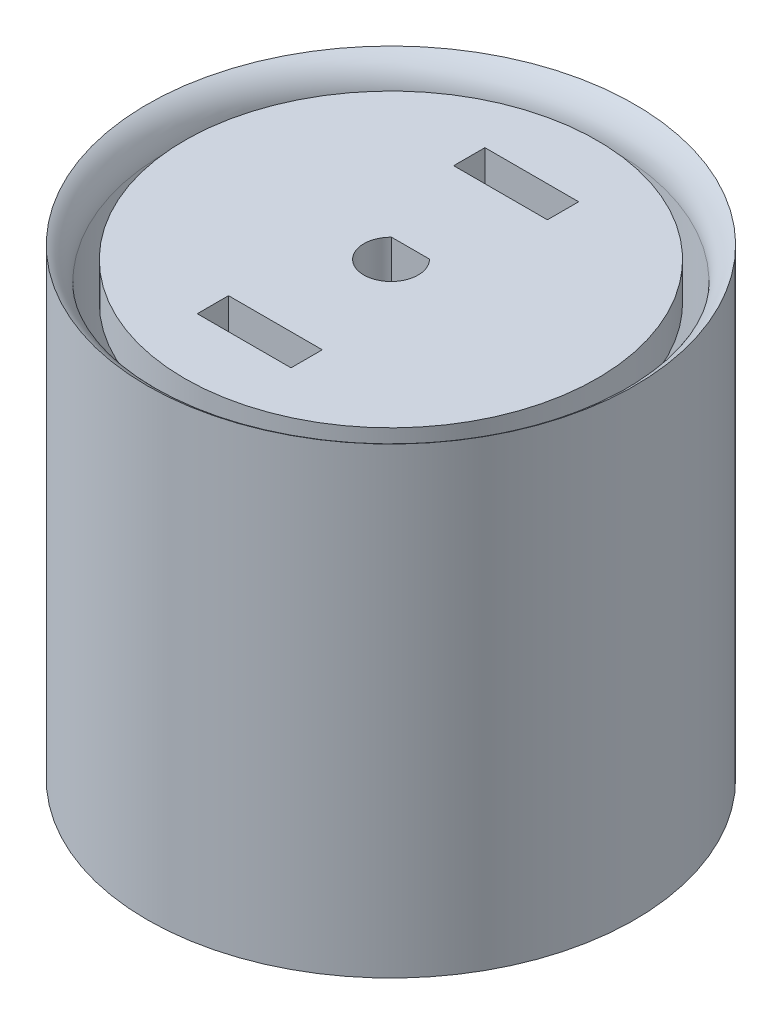
SolidWorks part; units mm, degrees
ref_plane "Front Plane" through (0, 0, 0) normal (0, 0, 1) x (1, 0, 0)
ref_plane "Top Plane" through (0, 0, 0) normal (0, 1, 0) x (1, 0, 0)
ref_plane "Right Plane" through (0, 0, 0) normal (1, 0, 0) x (0, 0, -1)
ref_plane "Plane1" through (0, -15, 0) normal (0, 1, 0) x (1, 0, 0)
ref_plane "Plane2" through (0, 21, 0) normal (0, 1, 0) x (1, 0, 0)
sketch "Sketch1" plane through (0, -15, 0) normal (0, 1, 0) x (1, 0, 0)
  circle A0 centre (0, 0) radius 17
  dimension "D1" = 34
extrude "Boss-Extrude1" add sketch "Sketch1" along normal blind 3
sketch "Sketch3" plane through (0, 21, 0) normal (0, 1, 0) x (1, 0, 0)
  circle A0 centre (0, 0) radius 17
  dimension "D1" = 34
extrude "Boss-Extrude2" add sketch "Sketch3" against normal blind 3 separate body
ref_plane "Plane3" through (0, -12, 0) normal (0, 1, 0) x (1, 0, 0)
sketch "Sketch6" plane through (0, -12, 0) normal (0, 1, 0) x (1, 0, 0)
  line L0 (-10.3961, -6.8606) -> (-11.6878, -8.1522)
  line L1 (-11.6878, -8.1522) -> (-12.2448, -7.2889)
  line L2 (-12.2448, -7.2889) -> (-12.7381, -6.3877)
  line L3 (-12.7381, -6.3877) -> (-13.1653, -5.4532)
  line L4 (-13.1653, -5.4532) -> (-13.524, -4.4905)
  line L5 (-13.524, -4.4905) -> (-13.8124, -3.5043)
  line L6 (-13.8124, -3.5043) -> (-14.029, -2.5)
  line L7 (-14.029, -2.5) -> (-12.2023, -2.5)
  line L8 (-12.2023, -2.5) -> (-12.2023, 2.5)
  line L9 (-12.2023, 2.5) -> (-14.029, 2.5)
  line L10 (-14.029, 2.5) -> (-13.8124, 3.5043)
  line L11 (-13.8124, 3.5043) -> (-13.524, 4.4905)
  line L12 (-13.524, 4.4905) -> (-13.1653, 5.4532)
  line L13 (-13.1653, 5.4532) -> (-12.7381, 6.3877)
  line L14 (-12.7381, 6.3877) -> (-12.2448, 7.2889)
  line L15 (-12.2448, 7.2889) -> (-11.6878, 8.1522)
  line L16 (-11.6878, 8.1522) -> (-10.3961, 6.8606)
  line L17 (-10.3961, 6.8606) -> (-6.8606, 10.3961)
  line L18 (-6.8606, 10.3961) -> (-8.1522, 11.6878)
  line L19 (-8.1522, 11.6878) -> (-7.2889, 12.2448)
  line L20 (-7.2889, 12.2448) -> (-6.3877, 12.7381)
  line L21 (-6.3877, 12.7381) -> (-5.4532, 13.1653)
  line L22 (-5.4532, 13.1653) -> (-4.4905, 13.524)
  line L23 (-4.4905, 13.524) -> (-3.5043, 13.8124)
  line L24 (-3.5043, 13.8124) -> (-2.5, 14.029)
  line L25 (-2.5, 14.029) -> (-2.5, 12.1742)
  line L26 (-2.5, 12.1742) -> (2.5, 12.2023)
  line L27 (2.5, 12.2023) -> (2.5, 14.029)
  line L28 (2.5, 14.029) -> (3.5043, 13.8124)
  line L29 (3.5043, 13.8124) -> (4.4905, 13.524)
  line L30 (4.4905, 13.524) -> (5.4532, 13.1653)
  line L31 (5.4532, 13.1653) -> (6.3877, 12.7381)
  line L32 (6.3877, 12.7381) -> (7.2889, 12.2448)
  line L33 (7.2889, 12.2448) -> (8.1522, 11.6878)
  line L34 (8.1522, 11.6878) -> (6.8606, 10.3961)
  line L35 (6.8606, 10.3961) -> (10.3961, 6.8606)
  line L36 (10.3961, 6.8606) -> (11.6878, 8.1522)
  line L37 (11.6878, 8.1522) -> (12.2448, 7.2889)
  line L38 (12.2448, 7.2889) -> (12.7381, 6.3877)
  line L39 (12.7381, 6.3877) -> (13.1653, 5.4532)
  line L40 (13.1653, 5.4532) -> (13.524, 4.4905)
  line L41 (13.524, 4.4905) -> (13.8124, 3.5043)
  line L42 (13.8124, 3.5043) -> (14.029, 2.5)
  line L43 (14.029, 2.5) -> (12.2023, 2.5)
  line L44 (12.2023, 2.5) -> (12.2023, -2.5)
  line L45 (12.2023, -2.5) -> (14.029, -2.5)
  line L46 (14.029, -2.5) -> (13.8124, -3.5043)
  line L47 (13.8124, -3.5043) -> (13.524, -4.4905)
  line L48 (13.524, -4.4905) -> (13.1653, -5.4532)
  line L49 (13.1653, -5.4532) -> (12.7381, -6.3877)
  line L50 (12.7381, -6.3877) -> (12.2448, -7.2889)
  line L51 (12.2448, -7.2889) -> (11.6878, -8.1522)
  line L52 (11.6878, -8.1522) -> (10.3961, -6.8606)
  line L53 (10.3961, -6.8606) -> (6.8606, -10.3961)
  line L54 (6.8606, -10.3961) -> (8.1522, -11.6878)
  line L55 (8.1522, -11.6878) -> (7.2889, -12.2448)
  line L56 (7.2889, -12.2448) -> (6.3877, -12.7381)
  line L57 (6.3877, -12.7381) -> (5.4532, -13.1653)
  line L58 (5.4532, -13.1653) -> (4.4905, -13.524)
  line L59 (4.4905, -13.524) -> (3.5043, -13.8124)
  line L60 (3.5043, -13.8124) -> (2.5, -14.029)
  line L61 (2.5, -14.029) -> (2.5, -12.2023)
  line L62 (2.5, -12.2023) -> (-2.5, -12.2023)
  line L63 (-2.5, -12.2023) -> (-2.5, -14.029)
  line L64 (-2.5, -14.029) -> (-3.5043, -13.8124)
  line L65 (-3.5043, -13.8124) -> (-4.4905, -13.524)
  line L66 (-4.4905, -13.524) -> (-5.4532, -13.1653)
  line L67 (-5.4532, -13.1653) -> (-6.3877, -12.7381)
  line L68 (-6.3877, -12.7381) -> (-7.2889, -12.2448)
  line L69 (-7.2889, -12.2448) -> (-8.1522, -11.6878)
  line L70 (-8.1522, -11.6878) -> (-6.8606, -10.3961)
  line L71 (-6.8606, -10.3961) -> (-10.3961, -6.8606)
extrude "Boss-Extrude3" add sketch "Sketch6" along normal blind 31
sketch "Sketch7" plane through (-0.0686, 0, -12.1878) normal (-0.0056, 0, -1) x (-1, 0, 0.0056)
  line L0 (2.5686, 18) -> (-2.4313, 18) construction
  circle A0 centre (-0.1208, 16) radius 1.7514
  dimension "D1" = 2
extrude "Cut-Extrude11" cut sketch "Sketch7" against normal blind 50
sketch "Sketch2" plane through (0, -15, 0) normal (0, 1, 0) x (1, 0, 0)
  line L0 (1.5148, 1.5664) -> (-1.5212, 1.5664)
  arc A0 (1.5148, 1.5664) -> (-1.5212, 1.5664) centre (-0.0032, 0.0099) cw
extrude "Cut-Extrude1" cut sketch "Sketch2" along normal blind 50
sketch "Sketch8" plane through (0, -15, 0) normal (0, 1, 0) x (1, 0, 0)
  line L1 (-3.9871, 11.5054) -> (3.5129, 11.5054)
  line L2 (-3.9871, 11.5054) -> (-3.9871, 9.0054)
  line L3 (-3.9871, 9.0054) -> (3.5129, 9.0054)
  line L4 (3.5129, 11.5054) -> (3.5129, 9.0054)
  dimension "D1" = 7.5
  dimension "D2" = 2.5
extrude "Cut-Extrude12" cut sketch "Sketch8" along normal blind 40
ref_plane "Plane4" through (0, 0, 0) normal (0, 0, 1) x (1, 0, 0)
ref_plane "Plane5" through (0, 0, 0) normal (1, 0, 0) x (0, 0, -1)
mirror "Mirror1" about plane through (0, 0, 0) normal (0, 0, 1) of "Cut-Extrude12"
sketch "Sketch9" plane through (0, -15, 0) normal (0, 1, 0) x (1, 0, 0)
  circle A0 centre (0, 0) radius 19.5
  circle A1 centre (0, 0) radius 18
  dimension "D1" = 36
  dimension "D2" = 39
extrude "Boss-Extrude4" add sketch "Sketch9" along normal blind 37 separate body
fillet "Fillet1" radius 3 1 edges at (0, 22, 18)
sketch "Sketch10" plane through (0, 21, 0) normal (0, 1, 0) x (1, 0, 0)
  circle A0 centre (0, 0) radius 17
  circle A1 centre (0, 0) radius 16.5
  dimension "D1" = 33
extrude "Cut-Extrude13" cut sketch "Sketch10" against normal blind 3
sketch "Sketch11" plane through (0, -15, 0) normal (0, 1, 0) x (1, 0, 0)
  circle A0 centre (0, 0) radius 19.5
extrude "Boss-Extrude5" add sketch "Sketch11" along normal blind 3
